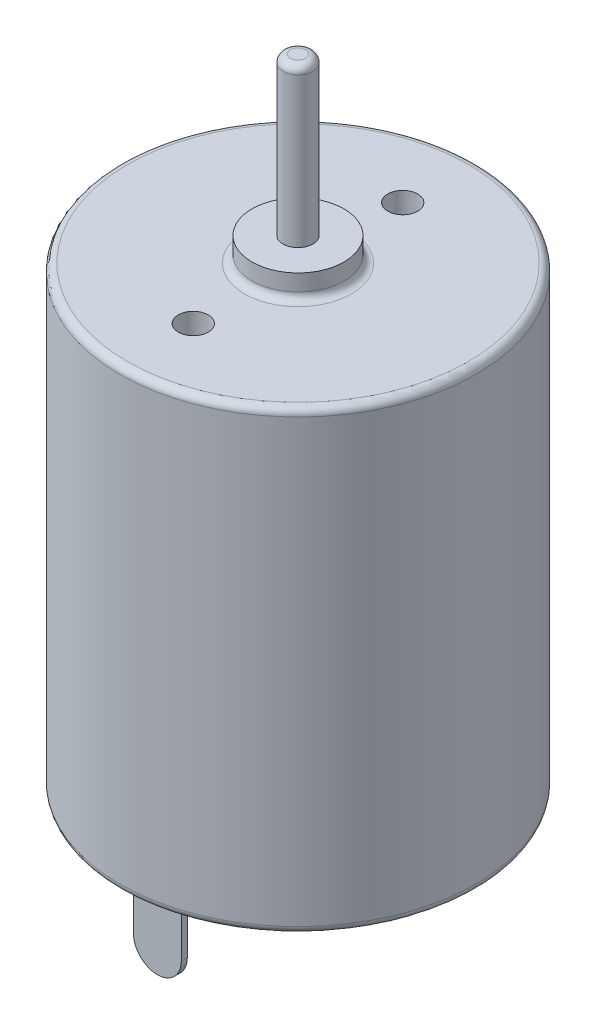
SolidWorks part; units mm, degrees
ref_plane "前基準面" through (0, 0, 0) normal (0, 0, 1) x (1, 0, 0)
ref_plane "上基準面" through (0, 0, 0) normal (0, 1, 0) x (1, 0, 0)
ref_plane "右基準面" through (0, 0, 0) normal (1, 0, 0) x (0, 0, -1)
sketch "草圖1" plane through (0, 0, 0) normal (0, 1, 0) x (1, 0, 0)
  circle A0 centre (0, 0) radius 11.9
  dimension "D1" = 23.8
extrude "填料-伸長1" add sketch "草圖1" along normal blind 30.5
sketch "草圖2" plane through (0, 0, 0) normal (0, -1, 0) x (1, 0, 0)
  line L0 (3.75, 2) -> (3.75, -2)
  circle A0 centre (0, 0) radius 4.25
  dimension "D1" = 8.5
  dimension "D2" = 3.75
extrude "填料-伸長2" add sketch "草圖2" along normal blind 1.5 contours L0 A0 region at (-0.0963, 0, 0)
sketch "草圖5" plane through (0, 0, 0) normal (0, -1, 0) x (1, 0, 0)
  line L0 (0, 9) -> (1.6, 9)
  line L1 (0, 9) -> (-1.6, 9)
  line L2 (-1.6, 9) -> (-1.6, 9.4)
  line L3 (-1.6, 9.4) -> (1.6, 9.4)
  line L4 (1.6, 9.4) -> (1.6, 9)
  line L5 (0, 0) -> (3.75, 0) construction
  line L6 (3.75, 2) -> (3.75, -2) construction
  line L7 (-1.6, -9.4) -> (1.6, -9.4)
  line L8 (-1.6, -9) -> (-1.6, -9.4)
  line L9 (0, -9) -> (-1.6, -9)
  line L10 (0, -9) -> (1.6, -9)
  line L11 (1.6, -9.4) -> (1.6, -9)
  circle A0 centre (0, 0) radius 9 construction
  point P8 (3.75, 0)
  dimension "D1" = 18
  dimension "D2" = 3.2
  dimension "D3" = 1.6
  dimension "D4" = 0.4
extrude "填料-伸長3" add sketch "草圖5" along normal blind 6
sketch "草圖6" plane through (0, 0, -9.4) normal (0, 0, -1) x (-1, 0, 0)
  line L2 (-1.6, -6) -> (1.6, -6) construction
  line L3 (-1.6, -6) -> (-1.6, 0) construction
  line L4 (-1.6, -4.4) -> (-1.6, -6)
  line L5 (-1.6, -6) -> (1.6, -6)
  line L6 (1.6, -6) -> (1.6, -4.4)
  arc A0 (-1.6, -4.4) -> (1.6, -4.4) centre (0, -4.4) ccw
  line M5 (-1.6, 0) -> (-1.6, -6)
  line M6 (-1.6, -6) -> (1.6, -6)
  line M7 (1.6, -6) -> (1.6, 0)
extrude "除料-伸長1" cut sketch "草圖6" against normal through all contours A0 L5 M7 | A0 M5 M6 region at (1.2426, -5.6426, -9.4) region at (-1.2426, -5.6426, -9.4)
sketch "草圖7" plane through (0, 30.5, 0) normal (0, 1, 0) x (1, 0, 0)
  line L0 (0, 0) -> (11.9, 0) construction
  circle A0 centre (0, 7) radius 1
  circle A2 centre (0, 0) radius 11.9 construction
  circle A3 centre (0, -7) radius 1
  dimension "D1" = 2
  dimension "D2" = 7
extrude "除料-伸長2" cut sketch "草圖7" against normal blind 5
sketch "草圖8" plane through (0, 30.5, 0) normal (0, 1, 0) x (1, 0, 0)
  circle A0 centre (0, 0) radius 3.075
  dimension "D1" = 6.15
extrude "填料-伸長4" add sketch "草圖8" along normal blind 1.6
sketch "草圖9" plane through (0, 32.1, 0) normal (0, 1, 0) x (1, 0, 0)
  circle A0 centre (0, 0) radius 1
  dimension "D1" = 2
extrude "填料-伸長5" add sketch "草圖9" along normal blind 10.5
fillet "圓角1" radius 0.5 1 edges at (0, 30.5, 3.075)
fillet "圓角2" radius 0.5 2 edges at (0, 0, 11.9) (0, 30.5, 11.9)
fillet "圓角3" radius 0.5 1 edges at (0, 42.6, 1)
